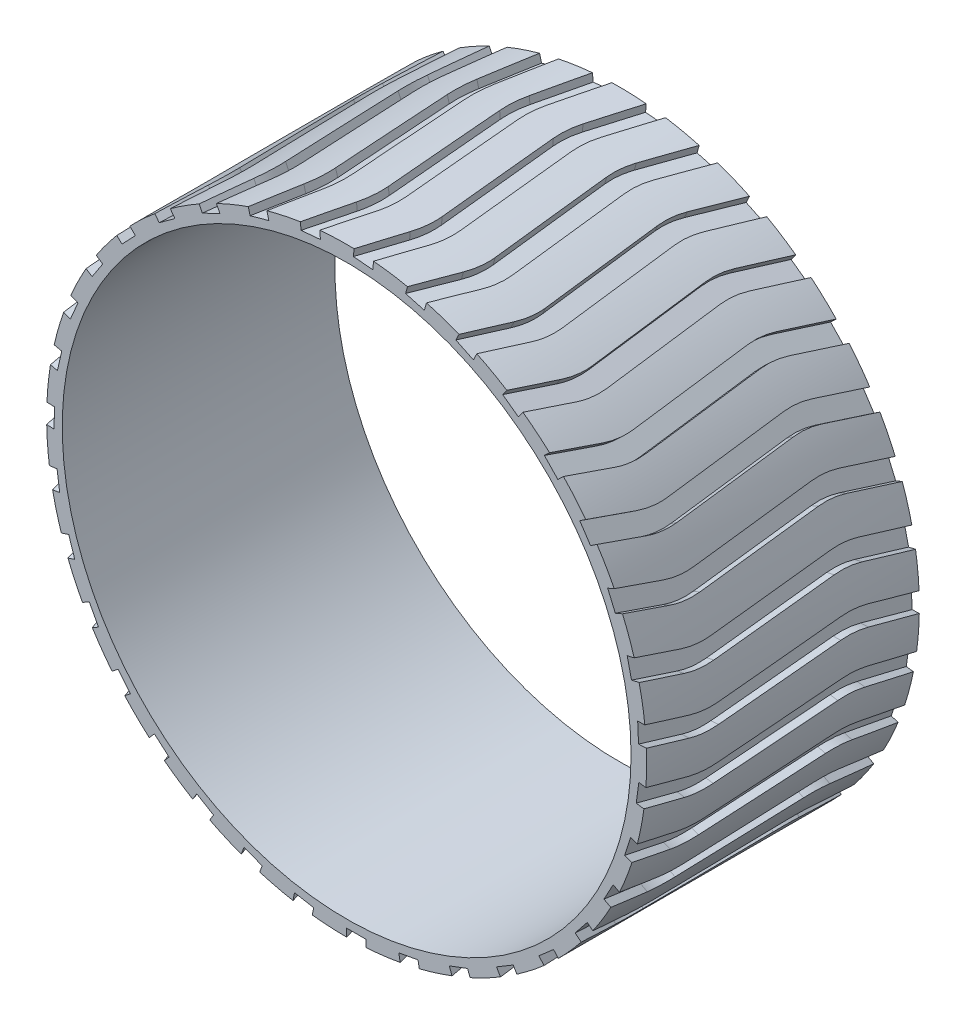
SolidWorks part; units mm, degrees
material "BUTYL"
ref_plane "Front Plane" through (0, 0, 0) normal (0, 0, 1) x (1, 0, 0)
ref_plane "Top Plane" through (0, 0, 0) normal (0, 1, 0) x (1, 0, 0)
ref_plane "Right Plane" through (0, 0, 0) normal (1, 0, 0) x (0, 0, -1)
sketch "Sketch1" plane through (0, 0, 0) normal (0, 0, 1) x (1, 0, 0)
  circle A0 centre (0, 0) radius 77
  circle A1 centre (0, 0) radius 73
  dimension "D1" = 154
  dimension "D2" = 146
extrude "Boss-Extrude1" add sketch "Sketch1" along normal blind 70
sketch "Sketch3" plane through (0, 0, 0) normal (0, 1, 0) x (1, 0, 0)
  line L0 (0, 0) -> (0, -70) construction
  line L4 (-77, -70) -> (77, -70) construction
  line L6 (0, 0) -> (-5, 0)
  line L7 (77, 0) -> (-77, 0) construction
  line L8 (-5, 0) -> (-1.5163, -13.0658)
  line L9 (-0.9296, -20.0968) -> (-3.9003, -51.5865)
  line L10 (-3.189, -59.0638) -> (0, -70)
  line L11 (0, 0) -> (3.4174, -12.817)
  line L12 (4.0041, -19.848) -> (1.0319, -51.3538)
  line L13 (1.7431, -58.831) -> (5, -70)
  line L14 (5, -70) -> (0, -70)
  arc A0 (3.4174, -12.817) -> (4.0041, -19.848) centre (-15.9075, -17.9695) cw
  arc A1 (-1.5163, -13.0658) -> (-0.9296, -20.0968) centre (-20.8412, -18.2183) cw
  arc A2 (1.0319, -51.3538) -> (1.7431, -58.831) centre (20.9435, -53.2322) ccw
  arc A3 (-3.9003, -51.5865) -> (-3.189, -59.0638) centre (16.0113, -53.4649) ccw
  point P1 (-4.2594, -55.3931)
  point P6 (0, -35)
  point P15 (0, 0)
  dimension "D3" = 20
  dimension "D1" = 5
  dimension "D2" = 5
extrude "Cut-Extrude2" cut sketch "Sketch3" against normal blind 5 from offset 75 offset against normal yes
pattern_circular "CirPattern1" count 35 over 360 about axis through (0, 0, 70) along (0, 0, -1) of "Cut-Extrude2" reverse direction yes
